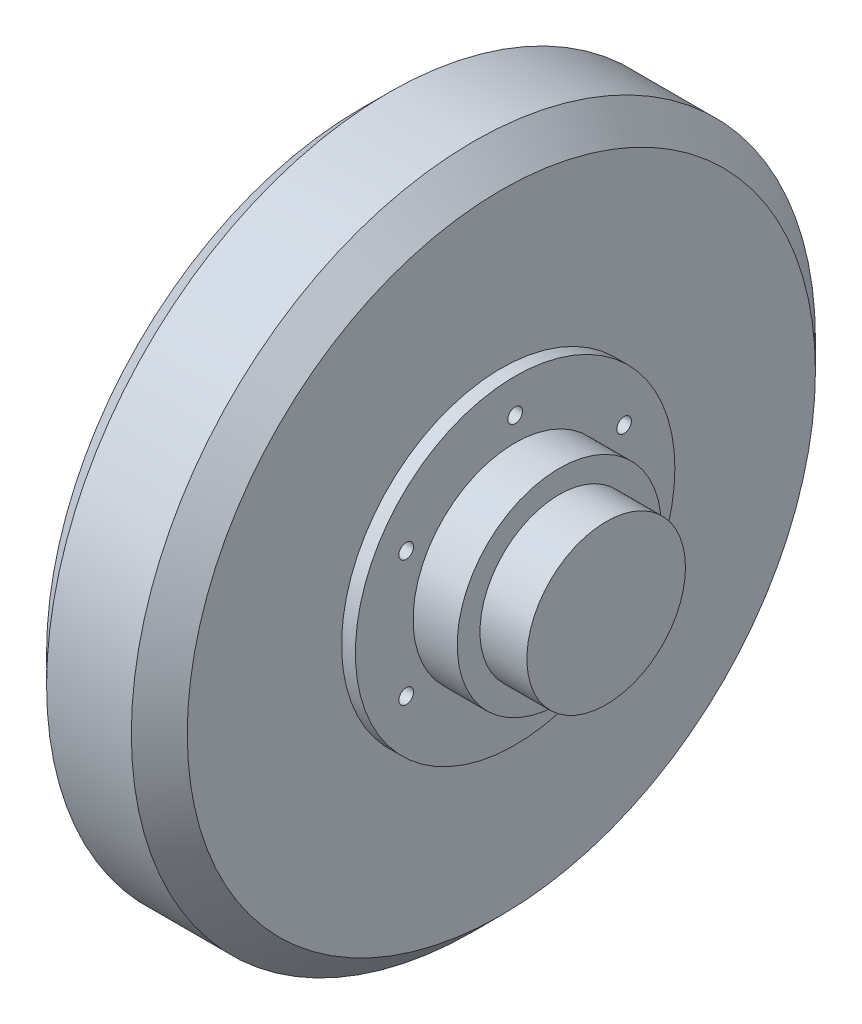
SolidWorks part; units mm, degrees
ref_plane "Front Plane" through (0, 0, 0) normal (1, 0, 0) x (0, 1, 0)
ref_plane "Top Plane" through (0, 0, 0) normal (0, 0, 1) x (0, 1, 0)
ref_plane "Right Plane" through (0, 0, 0) normal (0, 1, 0) x (-1, 0, 0)
sketch "Sketch1" plane through (0, 0, 0) normal (0, 1, 0) x (-1, 0, 0)
  line L0 (0, 73.5501) -> (6.35, 73.5501)
  line L1 (0, 0) -> (71.12, 0)
  line L2 (0, 0) -> (0, 157.48)
  line L3 (0, 157.48) -> (71.12, 157.48)
  line L4 (71.12, 0) -> (71.12, 157.48)
  line L5 (6.35, 73.5501) -> (6.35, 144.6057)
  line L6 (6.35, 144.6057) -> (19.2243, 157.48)
  line L7 (58.2457, 157.48) -> (71.12, 144.6057)
  line L9 (0, 0) -> (-20.32, 0)
  line L10 (0, 0) -> (0, 46.99)
  line L11 (0, 46.99) -> (-20.32, 46.99)
  line L12 (-20.32, 0) -> (-20.32, 46.99)
  line L13 (71.12, 0) -> (83.82, 0)
  line L14 (71.12, 0) -> (71.12, 14.9987)
  line L15 (71.12, 14.9987) -> (83.82, 14.9987)
  line L16 (83.82, 0) -> (83.82, 14.9987)
  line L17 (83.82, 0) -> (90.17, 0)
  line L18 (83.82, 0) -> (83.82, 24.13)
  line L19 (83.82, 24.13) -> (90.17, 24.13)
  line L20 (90.17, 0) -> (90.17, 24.13)
  line L21 (-20.32, 0) -> (-41.91, 0)
  line L22 (-20.32, 0) -> (-20.32, 36.5125)
  line L23 (-20.32, 36.5125) -> (-41.91, 36.5125)
  line L24 (-41.91, 0) -> (-41.91, 36.5125)
  dimension "D1" = 157.48
  dimension "D2" = 71.12
  dimension "D3" = 12.7
  dimension "D4" = 6.35
  dimension "D5" = 14.9987
  dimension "D6" = 24.13
  dimension "D7" = 20.32
  dimension "D8" = 45
  dimension "D9" = 45
  dimension "D10" = 6.35
  dimension "D11" = 46.99
  dimension "D13" = 36.5125
  dimension "D14" = 132.08
revolve "Revolve1" add sketch "Sketch1" angle 360 about L1 region at (-37.1535, 0, 75.6985) region at (10.16, 0, 23.495) region at (-77.47, 0, 7.4993) region at (31.115, 0, 18.2562) region at (-86.995, 0, 12.065)
sketch "Sketch2" plane through (-71.12, 0, 0) normal (-1, 0, 0) x (0, -1, 0)
  line L1 (0, -38.1) -> (36.2353, -11.7735)
  line L2 (36.2353, -11.7735) -> (22.3946, 30.8235)
  line L3 (22.3946, 30.8235) -> (-22.3946, 30.8235)
  line L4 (-22.3946, 30.8235) -> (-36.2353, -11.7735)
  line L5 (-36.2353, -11.7735) -> (0, -38.1)
  circle A0 centre (0, 0) radius 38.1
  circle A1 centre (0, 0) radius 144.6057
  circle A2 centre (0, 0) radius 144.6057
  circle A3 centre (0, 0) radius 30.8235 construction
  dimension "D2" = 76.2
  dimension "D1" = 0
sketch "Sketch3" plane through (-71.12, 0, 0) normal (-1, 0, 0) x (0, -1, 0)
  circle A0 centre (-22.3946, 30.8235) radius 3.3734
  circle A1 centre (22.3946, 30.8235) radius 3.3734
  circle A2 centre (36.2353, -11.7735) radius 3.3734
  circle A3 centre (0, -38.1) radius 3.3734
  circle A4 centre (-36.2353, -11.7735) radius 3.3734
  point P0 (-36.2353, -11.7735)
  point P2 (0, -38.1)
  point P4 (36.2353, -11.7735)
  point P6 (22.3946, 30.8235)
  point P8 (-22.3946, 30.8235)
  dimension "D1" = 6.7469
extrude "Cut-Extrude1" cut sketch "Sketch3" against normal blind 11.43
sketch "Sketch4" plane through (0, 0, 0) normal (1, 0, 0) x (0, 1, 0)
  line L0 (28.956, -50.1533) -> (57.912, 0)
  line L1 (57.912, 0) -> (28.956, 50.1533)
  line L2 (28.956, 50.1533) -> (-28.956, 50.1533)
  line L3 (-28.956, 50.1533) -> (-57.912, 0)
  line L4 (-57.912, 0) -> (-28.956, -50.1533)
  line L5 (-28.956, -50.1533) -> (28.956, -50.1533)
  circle A0 centre (0, 0) radius 50.1533 construction
  circle A1 centre (0, 0) radius 73.5501
  circle A2 centre (0, 0) radius 73.5501
  circle A3 centre (28.956, 50.1533) radius 3.3734
  dimension "D3" = 6.7469
  dimension "D2" = 115.824
  dimension "D1" = 0
sketch "Sketch5" plane through (0, 0, 0) normal (1, 0, 0) x (0, 1, 0)
  circle A0 centre (28.956, 50.1533) radius 3.3734 construction
  circle A1 centre (28.956, 50.1533) radius 3.3734
  circle A2 centre (-28.956, 50.1533) radius 3.3734
  circle A3 centre (-57.912, 0) radius 3.3734
  circle A4 centre (-28.956, -50.1533) radius 3.3734
  circle A5 centre (28.956, -50.1533) radius 3.3734
  circle A6 centre (57.912, 0) radius 3.3734
  point P0 (28.956, -50.1533)
  point P2 (57.912, 0)
  point P4 (28.956, 50.1533)
  point P9 (-28.956, -50.1533)
  point P11 (-57.912, 0)
  point P13 (-28.956, 50.1533)
extrude "Cut-Extrude2" cut sketch "Sketch5" against normal blind 12.7
equation "\"D9@Sketch1\"=\"D8@Sketch1\""
